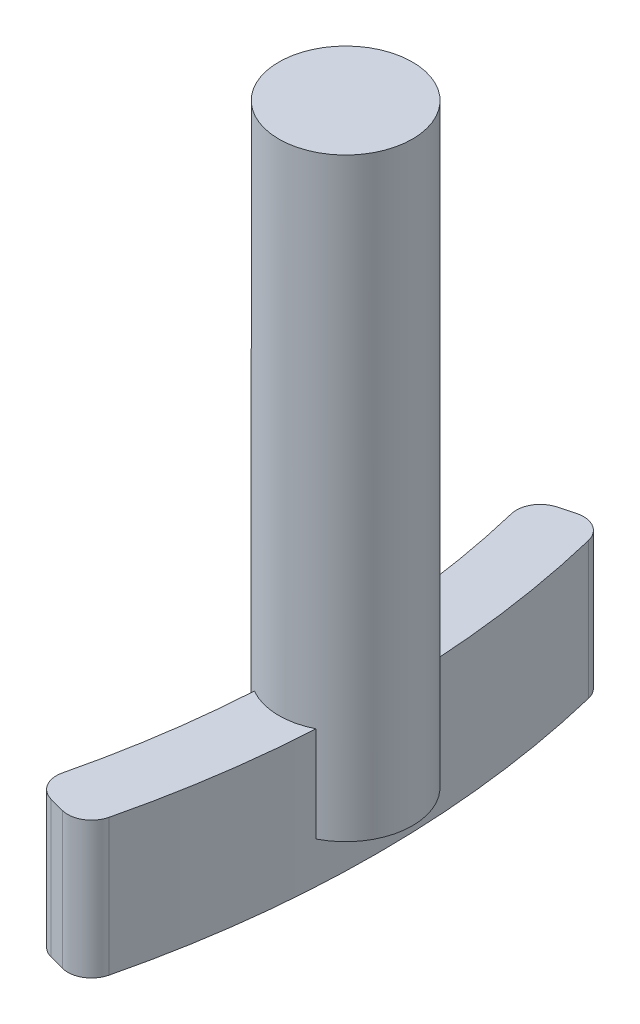
SolidWorks part; units mm, degrees
material "ABS"
ref_plane "Front Plane" through (0, 0, 0) normal (0, 0, 1) x (1, 0, 0)
ref_plane "Top Plane" through (0, 0, 0) normal (0, 1, 0) x (1, 0, 0)
ref_plane "Right Plane" through (0, 0, 0) normal (1, 0, 0) x (0, 0, -1)
sketch "Эскиз1" plane through (0, 0, 0) normal (0, 1, 0) x (1, 0, 0)
  line L10 (-0.8754, -7.9563) -> (-0.3923, -8.0858)
  line L11 (-0.8754, 7.9563) -> (-0.3923, 8.0858)
  arc A30 (0.5307, -7.538) -> (-0.3923, -8.0858) centre (-0.1981, -7.3613) cw
  arc A31 (0.5307, -7.538) -> (0.5307, 7.538) centre (-30.5687, 0) ccw
  arc A32 (-0.3923, 8.0858) -> (0.5307, 7.538) centre (-0.1981, 7.3613) cw
  arc A33 (-0.8754, 7.9563) -> (-1.4102, 7.0555) centre (-0.6813, 7.2319) ccw
  arc A34 (-1.4102, -7.0555) -> (-1.4102, 7.0555) centre (-30.5687, 0) ccw
  arc A35 (-0.8754, -7.9563) -> (-1.4102, -7.0555) centre (-0.6813, -7.2319) cw
  point P29 (-0.1172, -8.1069)
  point P30 (0.3409, 8.2822)
  point P32 (-0.1172, 8.1069)
extrude "Бобышка-Вытянуть1" add sketch "Эскиз1" along normal blind 4.3
ref_plane "Плоскость1" through (0, 1.3, 0) normal (0, 1, 0) x (1, 0, 0)
sketch "Эскиз2" plane through (0, 1.3, 0) normal (0, 1, 0) x (1, 0, 0)
  circle A2 centre (0.4313, 0) radius 2.1
  dimension "D1" = 4.2
extrude "Бобышка-Вытянуть2" add sketch "Эскиз2" along normal blind 18.7
